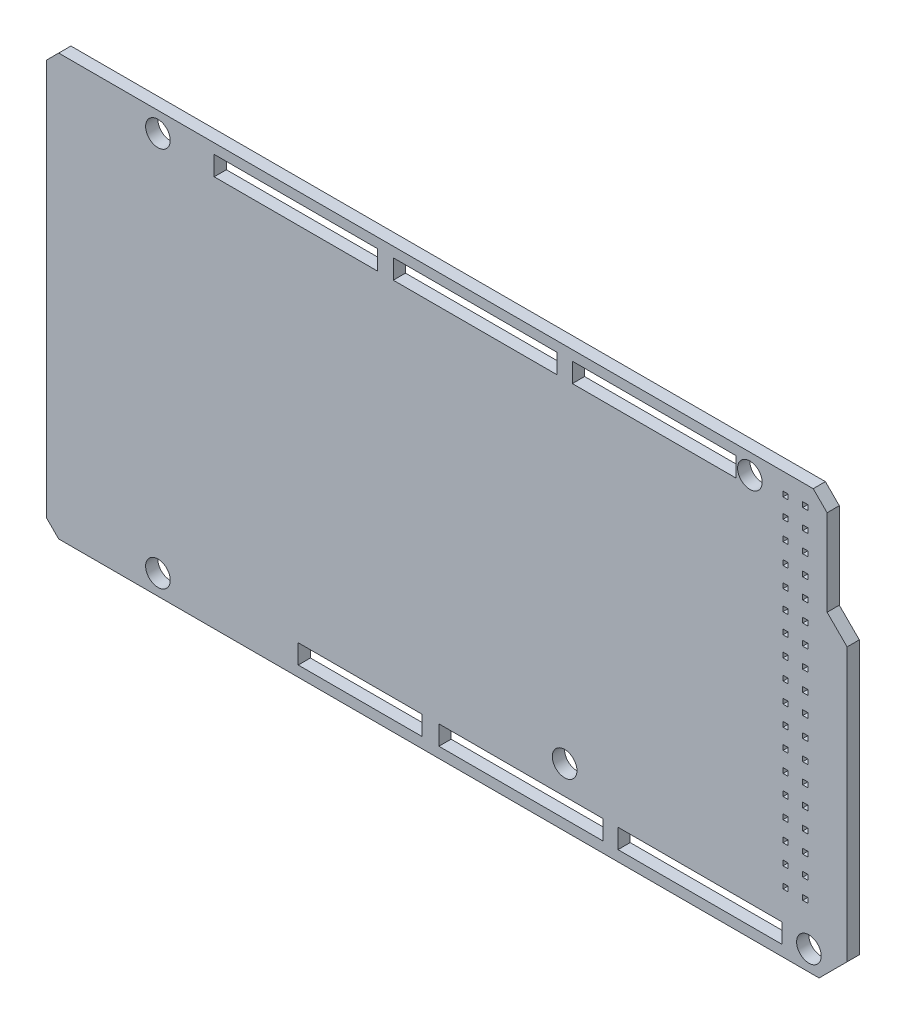
SolidWorks part; units mm, degrees
note: The reader was unsure of these and kept them because the rebuilt part matched: shared geometry of "Croquis3<3>".
ref_plane "Alzado" through (0, 0, 0) normal (0, 0, 1) x (1, 0, 0)
ref_plane "Planta" through (0, 0, 0) normal (0, 1, 0) x (1, 0, 0)
ref_plane "Vista lateral" through (0, 0, 0) normal (1, 0, 0) x (0, 0, -1)
sketch "Croquis1" plane through (0, 0, 0) normal (0, 0, 1) x (1, 0, 0)
  line L14 (46.5466, 27.6032) -> (48.31, 25.8397)
  line L15 (48.31, 25.8397) -> (48.31, 14.9032)
  line L16 (48.31, 14.9032) -> (50.85, 12.3632)
  line L17 (50.85, 12.3632) -> (50.85, -22.257)
  line L18 (47.294, -25.813) -> (50.85, -22.257)
  line L19 (47.294, -25.813) -> (-49.226, -25.813)
  line L20 (-50.75, -24.289) -> (-49.226, -25.813)
  line L21 (-50.75, -24.289) -> (-50.75, -22.003)
  line L22 (-50.75, -22.003) -> (-50.75, -12.859)
  line L23 (-50.75, 6.3942) -> (-50.75, 18.3322)
  line L24 (-50.75, -12.859) -> (-50.75, 6.3942)
  line L25 (-49.226, 27.6032) -> (46.5466, 27.6032)
  line L26 (-49.226, 27.6032) -> (-50.75, 26.0792)
  line L27 (-50.75, 18.3322) -> (-50.75, 26.0792)
  line L28 (-29.4902, 26.3332) -> (-29.4902, 23.8694)
  line L29 (-8.7384, 26.3332) -> (-29.4902, 26.3332)
  line L30 (-29.4902, 23.8694) -> (-8.7384, 23.8694)
  line L31 (-8.7384, 23.8694) -> (-8.7384, 26.3332)
  line L32 (-6.7572, 26.3332) -> (-6.7572, 23.8694)
  line L33 (13.9946, 26.3332) -> (-6.7572, 26.3332)
  line L34 (-6.7572, 23.8694) -> (13.9946, 23.8694)
  line L35 (15.9758, 26.3332) -> (15.9758, 23.8694)
  line L36 (36.7276, 26.3332) -> (15.9758, 26.3332)
  line L37 (15.9758, 23.8694) -> (36.7276, 23.8694)
  line L38 (36.7276, 23.8694) -> (36.7276, 26.3332)
  line L39 (46.786, 26.384) -> (41.8076, 26.384)
  line L40 (41.8076, 26.384) -> (41.8076, -19.8948)
  line L41 (46.786, -19.8948) -> (46.786, 26.384)
  line L42 (41.8076, -19.8948) -> (46.786, -19.8948)
  line L43 (42.595, -24.4668) -> (42.595, -22.003)
  line L44 (21.767, -24.4668) -> (42.595, -24.4668)
  line L45 (21.767, -22.003) -> (21.767, -24.4668)
  line L46 (19.862, -24.4668) -> (19.862, -22.003)
  line L47 (42.595, -22.003) -> (21.767, -22.003)
  line L48 (19.862, -22.003) -> (-0.966, -22.003)
  line L49 (-0.966, -24.4668) -> (19.862, -24.4668)
  line L50 (-0.966, -22.003) -> (-0.966, -24.4668)
  line L51 (-3.125, -24.4668) -> (-3.125, -22.0174)
  line L52 (-3.125, -22.0174) -> (-18.8222, -22.0174)
  line L53 (-18.8222, -24.4668) -> (-3.125, -24.4668)
  line L54 (-18.8222, -22.0174) -> (-18.8222, -24.4668)
  line L55 (13.9946, 26.3332) -> (13.9946, 23.8694)
  circle A5 centre (-36.6276, -23.273) radius 1.5621
  circle A6 centre (14.9979, -18.3945) radius 1.5621
  circle A7 centre (45.9986, -23.273) radius 1.5621
  circle A8 centre (-36.6276, 25.0632) radius 1.5621
  circle A9 centre (38.5056, 25.0632) radius 1.5621
  point P26 (-49.988, 26.8412)
  point P53 (0, 0)
  point P54 (0, 0)
extrude "Saliente-Extruir1" add sketch "Croquis1" along normal blind 1.55
sketch "Croquis2" plane through (0, 0, 0) normal (0, 0, -1) x (-1, 0, 0)
  line L1 (-46.786, 26.384) -> (-41.786, 26.384)
  line L2 (-46.786, 26.384) -> (-46.786, -19.8948)
  line L3 (-46.786, -19.8948) -> (-41.786, -19.8948)
  line L4 (-41.786, 26.384) -> (-41.786, -19.8948)
  dimension "D1" = 5
extrude "Cortar-Extruir1" cut sketch "Croquis2" against normal blind 95.55
sketch "Croquis3" plane through (0, 0, 0) normal (0, 0, -1) x (-1, 0, 0)
  line L0 (-46.786, 26.384) -> (-46.786, 25.104) construction
  line L1 (-46.786, -19.8948) -> (-46.786, 26.384) construction
  line L2 (-46.786, 25.104) -> (-41.786, 25.104) construction
  line L3 (-43.36, 20.5067) -> (-42.72, 20.5067)
  line L4 (-45.8587, 24.8652) -> (-45.2187, 24.8652)
  line L5 (-45.8587, 24.8652) -> (-45.8587, 25.5052)
  line L6 (-45.8587, 25.5052) -> (-45.2187, 25.5052)
  line L7 (-45.2187, 24.8652) -> (-45.2187, 25.5052)
  line L8 (-45.8587, 24.8652) -> (-45.2187, 25.5052) construction
  line L9 (-45.8587, 25.5052) -> (-45.2187, 24.8652) construction
  line L10 (-42.72, 20.5067) -> (-42.72, 19.866)
  line L11 (-43.36, 24.7836) -> (-42.72, 24.7836)
  line L12 (-43.36, 24.7836) -> (-43.36, 25.4243)
  line L13 (-43.36, 25.4243) -> (-42.72, 25.4243)
  line L14 (-42.72, 24.7836) -> (-42.72, 25.4243)
  line L15 (-43.36, 24.7836) -> (-42.72, 25.4243) construction
  line L16 (-43.36, 25.4243) -> (-42.72, 24.7836) construction
  line L17 (-41.786, -19.8948) -> (-41.786, 26.384) construction
  line L18 (-44.286, 25.104) -> (-44.286, 26.384) construction
  line L19 (-46.786, 22.6452) -> (-41.786, 22.6452) construction
  line L20 (-45.5387, 25.1852) -> (-45.5387, -19.8948) construction
  line L21 (-44.286, 25.104) -> (-44.286, -19.8948) construction
  line L22 (-41.786, -19.8948) -> (-46.786, -19.8948) construction
  line L23 (-43.04, 25.104) -> (-43.04, -19.8948) construction
  line L24 (-46.786, 20.1052) -> (-41.786, 20.1052) construction
  line L25 (-46.786, 17.5652) -> (-41.786, 17.5652) construction
  line L26 (-46.786, 15.0252) -> (-41.786, 15.0252) construction
  line L27 (-46.786, 12.4852) -> (-41.786, 12.4852) construction
  line L28 (-46.786, 9.9452) -> (-41.786, 9.9452) construction
  line L29 (-46.786, 7.4052) -> (-41.786, 7.4052) construction
  line L30 (-46.786, 4.8652) -> (-41.786, 4.8652) construction
  line L31 (-46.786, 2.3252) -> (-41.786, 2.3252) construction
  line L32 (-46.786, -0.2148) -> (-41.786, -0.2148) construction
  line L33 (-46.786, -2.7548) -> (-41.786, -2.7548) construction
  line L34 (-43.36, 19.866) -> (-42.72, 19.866)
  line L35 (-46.786, -5.2948) -> (-41.786, -5.2948) construction
  line L36 (-46.786, -7.8348) -> (-41.786, -7.8348)
  line L37 (-46.786, -10.3748) -> (-41.786, -10.3748) construction
  line L38 (-46.786, -12.9148) -> (-41.786, -12.9148) construction
  line L39 (-46.786, -15.4548) -> (-41.786, -15.4548) construction
  line L40 (-46.786, -17.9948) -> (-41.786, -17.9948) construction
  line L41 (-43.36, 20.5067) -> (-43.36, 19.866)
  line L42 (-45.2187, 20.4252) -> (-45.2187, 19.7852)
  line L43 (-45.8587, 20.4252) -> (-45.2187, 20.4252)
  line L44 (-45.8587, 22.9652) -> (-45.2187, 22.9652)
  line L45 (-45.8587, 22.9652) -> (-45.8587, 22.3252)
  line L46 (-45.8587, 22.3252) -> (-45.2187, 22.3252)
  line L47 (-45.2187, 22.9652) -> (-45.2187, 22.3252)
  line L48 (-45.8587, 22.9652) -> (-45.2187, 22.3252) construction
  line L49 (-45.8587, 22.3252) -> (-45.2187, 22.9652) construction
  line L50 (-45.8587, 20.4252) -> (-45.8587, 19.7852)
  line L51 (-45.8587, 19.7852) -> (-45.2187, 19.7852)
  line L52 (-45.5387, 22.6452) -> (-43.036, 22.6452) construction
  line L53 (-45.8587, 19.7852) -> (-45.8587, 15.0252) construction
  line L54 (-43.356, 22.3252) -> (-42.716, 22.3252)
  line L55 (-43.356, 22.3252) -> (-43.356, 22.9652)
  line L56 (-43.356, 22.9652) -> (-42.716, 22.9652)
  line L57 (-42.716, 22.3252) -> (-42.716, 22.9652)
  line L58 (-43.356, 22.3252) -> (-42.716, 22.9652) construction
  line L59 (-43.356, 22.9652) -> (-42.716, 22.3252) construction
  line L60 (-45.2187, 19.7852) -> (-45.2187, 15.0252) construction
  line L61 (-45.8587, 15.0252) -> (-45.8587, -0.2148) construction
  line L62 (-45.2187, 15.0252) -> (-45.2187, -0.2148) construction
  line L63 (-45.8587, -0.2148) -> (-45.8587, -19.8948) construction
  line L64 (-45.2187, -0.2148) -> (-45.2187, -19.8948) construction
  line L65 (-43.36, 19.866) -> (-43.36, 17.5652) construction
  line L70 (-42.72, 19.866) -> (-42.72, 17.5652) construction
  line L71 (-43.36, 17.5652) -> (-43.36, 15.0252) construction
  line L72 (-42.72, 17.5652) -> (-42.72, 15.0252) construction
  line L73 (-43.36, 15.0252) -> (-43.36, 7.4052) construction
  line L74 (-42.72, 15.0252) -> (-42.72, 4.8652) construction
  line L75 (-42.72, 4.8652) -> (-42.72, -19.8948) construction
  line L76 (-43.36, 7.4052) -> (-43.36, -19.8948) construction
  line L77 (-45.5387, -17.9948) -> (-43.04, -17.9948) construction
  line L78 (-45.8587, -18.3148) -> (-45.2187, -18.3148)
  line L79 (-45.8587, -18.3148) -> (-45.8587, -17.6748)
  line L80 (-45.8587, -17.6748) -> (-45.2187, -17.6748)
  line L81 (-45.2187, -18.3148) -> (-45.2187, -17.6748)
  line L82 (-45.8587, -18.3148) -> (-45.2187, -17.6748) construction
  line L83 (-45.8587, -17.6748) -> (-45.2187, -18.3148) construction
  line L84 (-43.36, -12.5948) -> (-42.72, -12.5948)
  line L85 (-43.36, -18.3148) -> (-42.72, -18.3148)
  line L86 (-43.36, -18.3148) -> (-43.36, -17.6748)
  line L87 (-43.36, -17.6748) -> (-42.72, -17.6748)
  line L88 (-42.72, -18.3148) -> (-42.72, -17.6748)
  line L89 (-43.36, -18.3148) -> (-42.72, -17.6748) construction
  line L90 (-43.36, -17.6748) -> (-42.72, -18.3148) construction
  line L91 (-42.72, -12.5948) -> (-42.72, -13.2348)
  line L92 (-43.36, -13.2348) -> (-42.72, -13.2348)
  line L93 (-43.36, -12.5948) -> (-43.36, -13.2348)
  line L94 (-45.2187, -12.5948) -> (-45.2187, -13.2348)
  line L95 (-45.8587, -12.5948) -> (-45.2187, -12.5948)
  line L96 (-45.8587, -12.5948) -> (-45.8587, -13.2348)
  line L97 (-45.8587, -13.2348) -> (-45.2187, -13.2348)
  line L98 (-46.786, -15.4548) -> (-45.5387, -15.4548) construction
  line L99 (-45.5387, -15.4548) -> (-43.04, -15.4548) construction
  line L100 (-46.786, -10.3748) -> (-45.5387, -10.3748) construction
  line L101 (-45.8587, -15.7748) -> (-45.2187, -15.7748)
  line L102 (-45.8587, -15.7748) -> (-45.8587, -15.1348)
  line L103 (-45.8587, -15.1348) -> (-45.2187, -15.1348)
  line L104 (-45.2187, -15.7748) -> (-45.2187, -15.1348)
  line L105 (-45.8587, -15.7748) -> (-45.2187, -15.1348) construction
  line L106 (-45.8587, -15.1348) -> (-45.2187, -15.7748) construction
  line L107 (-43.36, -15.7748) -> (-42.72, -15.7748)
  line L108 (-43.36, -15.7748) -> (-43.36, -15.1348)
  line L109 (-43.36, -15.1348) -> (-42.72, -15.1348)
  line L110 (-42.72, -15.7748) -> (-42.72, -15.1348)
  line L111 (-43.36, -15.7748) -> (-42.72, -15.1348) construction
  line L112 (-43.36, -15.1348) -> (-42.72, -15.7748) construction
  line L113 (-45.5387, -10.3748) -> (-43.04, -10.3748) construction
  line L114 (-43.36, -4.9748) -> (-42.72, -4.9748)
  line L115 (-45.8587, -10.6948) -> (-45.2187, -10.6948)
  line L116 (-45.8587, -10.6948) -> (-45.8587, -10.0548)
  line L117 (-45.8587, -10.0548) -> (-45.2187, -10.0548)
  line L118 (-45.2187, -10.6948) -> (-45.2187, -10.0548)
  line L119 (-45.8587, -10.6948) -> (-45.2187, -10.0548) construction
  line L120 (-45.8587, -10.0548) -> (-45.2187, -10.6948) construction
  line L121 (-43.36, -10.6948) -> (-42.72, -10.6948)
  line L122 (-43.36, -10.6948) -> (-43.36, -10.0548)
  line L123 (-43.36, -10.0548) -> (-42.72, -10.0548)
  line L124 (-42.72, -10.6948) -> (-42.72, -10.0548)
  line L125 (-43.36, -10.6948) -> (-42.72, -10.0548) construction
  line L126 (-43.36, -10.0548) -> (-42.72, -10.6948) construction
  line L127 (-42.72, -4.9748) -> (-42.72, -5.6148)
  line L128 (-43.36, -5.6148) -> (-42.72, -5.6148)
  line L129 (-43.36, -4.9748) -> (-43.36, -5.6148)
  line L130 (-45.2187, -4.9748) -> (-45.2187, -5.6148)
  line L131 (-45.8587, -4.9748) -> (-45.2187, -4.9748)
  line L132 (-45.8587, -4.9748) -> (-45.8587, -5.6148)
  line L133 (-45.8587, -5.6148) -> (-45.2187, -5.6148)
  line L134 (-46.786, -7.8348) -> (-45.5387, -7.8348) construction
  line L135 (-45.5387, -7.8348) -> (-43.04, -7.8348) construction
  line L136 (-45.2187, -7.5148) -> (-42.72, -7.5148) construction
  line L137 (-45.8586, -8.1548) -> (-45.2187, -8.1548)
  line L138 (-45.8586, -8.1548) -> (-45.8586, -7.5148)
  line L139 (-45.8586, -7.5148) -> (-45.2187, -7.5148)
  line L140 (-45.2187, -8.1548) -> (-45.2187, -7.5148)
  line L141 (-45.8586, -8.1548) -> (-45.2187, -7.5148) construction
  line L142 (-45.8586, -7.5148) -> (-45.2187, -8.1548) construction
  line L143 (-45.2187, -8.1548) -> (-42.72, -8.1548) construction
  line L144 (-46.786, -2.7548) -> (-45.5387, -2.7548) construction
  line L145 (-43.36, -8.1548) -> (-42.72, -8.1548)
  line L146 (-43.36, -8.1548) -> (-43.36, -7.5148)
  line L147 (-43.36, -7.5148) -> (-42.72, -7.5148)
  line L148 (-42.72, -8.1548) -> (-42.72, -7.5148)
  line L149 (-43.36, -8.1548) -> (-42.72, -7.5148) construction
  line L150 (-43.36, -7.5148) -> (-42.72, -8.1548) construction
  line L151 (-45.2187, -2.4348) -> (-42.72, -2.4348) construction
  line L152 (-45.8587, -3.0748) -> (-45.2187, -3.0748)
  line L153 (-45.8587, -3.0748) -> (-45.8587, -2.4348)
  line L154 (-45.8587, -2.4348) -> (-45.2187, -2.4348)
  line L155 (-45.2187, -3.0748) -> (-45.2187, -2.4348)
  line L156 (-45.8587, -3.0748) -> (-45.2187, -2.4348) construction
  line L157 (-45.8587, -2.4348) -> (-45.2187, -3.0748) construction
  line L158 (-45.2187, -3.0748) -> (-42.72, -3.0748) construction
  line L159 (-43.36, 2.6452) -> (-42.72, 2.6452)
  line L160 (-43.36, -3.0748) -> (-42.72, -3.0748)
  line L161 (-43.36, -3.0748) -> (-43.36, -2.4348)
  line L162 (-43.36, -2.4348) -> (-42.72, -2.4348)
  line L163 (-42.72, -3.0748) -> (-42.72, -2.4348)
  line L164 (-43.36, -3.0748) -> (-42.72, -2.4348) construction
  line L165 (-43.36, -2.4348) -> (-42.72, -3.0748) construction
  line L166 (-42.72, 2.6452) -> (-42.72, 2.0052)
  line L167 (-43.36, 2.0052) -> (-42.72, 2.0052)
  line L168 (-43.36, 2.6452) -> (-43.36, 2.0052)
  line L169 (-45.8587, 2.6452) -> (-45.2187, 2.6452)
  line L170 (-45.2187, 2.6452) -> (-45.2187, 2.0052)
  line L171 (-45.8587, 2.0052) -> (-45.2187, 2.0052)
  line L172 (-45.8587, 2.6452) -> (-45.8587, 2.0052)
  line L173 (-46.786, -0.2148) -> (-45.5387, -0.2148) construction
  line L174 (-45.5387, -0.2148) -> (-43.04, -0.2148) construction
  line L175 (-43.36, 7.7252) -> (-42.72, 7.7252)
  line L176 (-45.8587, -0.5348) -> (-45.2187, -0.5348)
  line L177 (-45.8587, -0.5348) -> (-45.8587, 0.1052)
  line L178 (-45.8587, 0.1052) -> (-45.2187, 0.1052)
  line L179 (-45.2187, -0.5348) -> (-45.2187, 0.1052)
  line L180 (-45.8587, -0.5348) -> (-45.2187, 0.1052) construction
  line L181 (-45.8587, 0.1052) -> (-45.2187, -0.5348) construction
  line L182 (-43.36, -0.5348) -> (-42.72, -0.5348)
  line L183 (-43.36, -0.5348) -> (-43.36, 0.1052)
  line L184 (-43.36, 0.1052) -> (-42.72, 0.1052)
  line L185 (-42.72, -0.5348) -> (-42.72, 0.1052)
  line L186 (-43.36, -0.5348) -> (-42.72, 0.1052) construction
  line L187 (-43.36, 0.1052) -> (-42.72, -0.5348) construction
  line L188 (-42.72, 7.0852) -> (-42.72, 7.7252)
  line L189 (-43.36, 7.0852) -> (-42.72, 7.0852)
  line L190 (-43.36, 7.0852) -> (-43.36, 7.7252)
  line L191 (-45.8587, 7.7252) -> (-45.2187, 7.7252)
  line L192 (-45.2187, 7.0852) -> (-45.2187, 7.7252)
  line L193 (-45.8587, 7.0852) -> (-45.8587, 7.7252)
  line L194 (-45.8587, 7.0852) -> (-45.2187, 7.0852)
  line L195 (-46.786, 4.8652) -> (-45.5387, 4.8652) construction
  line L196 (-45.5387, 4.8652) -> (-43.04, 4.8652) construction
  line L197 (-45.2187, 5.1852) -> (-42.72, 5.1852) construction
  line L198 (-45.8587, 4.5452) -> (-45.2187, 4.5452)
  line L199 (-45.8587, 4.5452) -> (-45.8587, 5.1852)
  line L200 (-45.8587, 5.1852) -> (-45.2187, 5.1852)
  line L201 (-45.2187, 4.5452) -> (-45.2187, 5.1852)
  line L202 (-45.8587, 4.5452) -> (-45.2187, 5.1852) construction
  line L203 (-45.8587, 5.1852) -> (-45.2187, 4.5452) construction
  line L204 (-45.2187, 4.5452) -> (-42.72, 4.5452) construction
  line L205 (-43.36, 5.1852) -> (-42.72, 5.1852)
  line L206 (-42.72, 5.1852) -> (-42.72, 4.5452)
  line L207 (-42.72, 4.5452) -> (-43.36, 4.5452)
  line L208 (-43.36, 4.5452) -> (-43.36, 5.1852)
  line L209 (-43.36, 12.8052) -> (-42.72, 12.8052)
  line L210 (-42.72, 12.8052) -> (-42.72, 12.1652)
  line L211 (-43.36, 12.1652) -> (-42.72, 12.1652)
  line L212 (-43.36, 12.8052) -> (-43.36, 12.1652)
  line L213 (-45.2187, 12.8052) -> (-45.2187, 12.1652)
  line L214 (-45.8587, 12.8052) -> (-45.2187, 12.8052)
  line L215 (-45.8587, 12.8052) -> (-45.8587, 12.1652)
  line L216 (-45.8587, 12.1652) -> (-45.2187, 12.1652)
  line L217 (-46.786, 9.9452) -> (-45.5387, 9.9452) construction
  line L218 (-45.5387, 9.9452) -> (-43.04, 9.9452) construction
  line L219 (-43.36, 17.8852) -> (-42.72, 17.8852)
  line L220 (-45.8587, 9.6252) -> (-45.2187, 9.6252)
  line L221 (-45.8587, 9.6252) -> (-45.8587, 10.2652)
  line L222 (-45.8587, 10.2652) -> (-45.2187, 10.2652)
  line L223 (-45.2187, 9.6252) -> (-45.2187, 10.2652)
  line L224 (-45.8587, 9.6252) -> (-45.2187, 10.2652) construction
  line L225 (-45.8587, 10.2652) -> (-45.2187, 9.6252) construction
  line L226 (-43.36, 9.6252) -> (-42.72, 9.6252)
  line L227 (-43.36, 9.6252) -> (-43.36, 10.2652)
  line L228 (-43.36, 10.2652) -> (-42.72, 10.2652)
  line L229 (-42.72, 9.6252) -> (-42.72, 10.2652)
  line L230 (-43.36, 9.6252) -> (-42.72, 10.2652) construction
  line L231 (-43.36, 10.2652) -> (-42.72, 9.6252) construction
  line L232 (-42.72, 17.2452) -> (-42.72, 17.8852)
  line L233 (-43.36, 17.2452) -> (-42.72, 17.2452)
  line L234 (-43.36, 17.2452) -> (-43.36, 17.8852)
  line L235 (-45.2187, 17.2452) -> (-45.2187, 17.8852)
  line L236 (-45.8587, 17.8852) -> (-45.2187, 17.8852)
  line L237 (-45.8587, 17.2452) -> (-45.8587, 17.8852)
  line L238 (-45.8587, 17.2452) -> (-45.2187, 17.2452)
  line L239 (-46.786, 15.0252) -> (-45.5387, 15.0252) construction
  line L240 (-45.5387, 15.0252) -> (-43.04, 15.0252) construction
  line L242 (-45.8587, 14.7052) -> (-45.2187, 14.7052)
  line L243 (-45.8587, 14.7052) -> (-45.8587, 15.3452)
  line L244 (-45.8587, 15.3452) -> (-45.2187, 15.3452)
  line L245 (-45.2187, 14.7052) -> (-45.2187, 15.3452)
  line L246 (-45.8587, 14.7052) -> (-45.2187, 15.3452) construction
  line L247 (-45.8587, 15.3452) -> (-45.2187, 14.7052) construction
  line L248 (-43.36, 14.7052) -> (-42.72, 14.7052)
  line L249 (-43.36, 14.7052) -> (-43.36, 15.3452)
  line L250 (-43.36, 15.3452) -> (-42.72, 15.3452)
  line L251 (-42.72, 14.7052) -> (-42.72, 15.3452)
  line L252 (-43.36, 14.7052) -> (-42.72, 15.3452) construction
  line L253 (-43.36, 15.3452) -> (-42.72, 14.7052) construction
  point P61 (-45.5387, 22.6452)
  point P83 (-45.5387, -17.9948)
  point P155 (-43.04, -2.7548)
  dimension "D1" = 1.28
  dimension "D2" = 1.25
  dimension "D3" = 0.64
  dimension "D4" = 0.64
  dimension "D5" = 2.5
  dimension "D6" = 0.64
  dimension "D7" = 2.54
  dimension "D8" = 2.54
  dimension "D9" = 2.54
  dimension "D18" = 2.54
  dimension "D24" = 0.64
  dimension "D25" = 0.64
  dimension "D26" = 0.64
  dimension "D27" = 0.64
  dimension "D28" = 0.64
  dimension "D29" = 0.64
  dimension "D30" = 0.64
  dimension "D31" = 0.64
  dimension "D32" = 0.64
  dimension "D33" = 0.64
  dimension "D34" = 0.64
  dimension "D35" = 0.64
  dimension "D36" = 0.64
  dimension "D37" = 0.64
  dimension "D38" = 0.64
  dimension "D39" = 0.64
  dimension "D40" = 0.64
  dimension "D10" = 2.54
  dimension "D11" = 2.54
  dimension "D12" = 2.54
  dimension "D13" = 2.54
  dimension "D14" = 2.54
  dimension "D15" = 2.54
  dimension "D16" = 2.54
  dimension "D17" = 2.54
  dimension "D19" = 2.54
  dimension "D20" = 2.54
  dimension "D21" = 2.54
  dimension "D22" = 2.54
  dimension "D23" = 2.54
extrude "Saliente-Extruir2" add sketch "Croquis3" against normal up to surface (1.55 mm away) contours L148 L145 L146 L36 L140 L137 L138 L79 L80 L88 L124 L121 L122 L123 L118 L115 L116 L117 L110 L107 L108 L109 L104 L101 L102 L103 L97 L96 L95 L94 L93 L84 L91 L92 L85 L86 L87 L81 L78
extrude "Saliente-Extruir3" add sketch "Croquis3<3>" against normal up to surface (1.55 mm away) contours L148 L36 L88 L87 L79 L138 L139 L140 L146 L147 L251 L248 L249 L250 L245 L242 L243 L244 L238 L237 L236 L235 L229 L226 L227 L228 L223 L220 L221 L222 L216 L215 L214 L213 L212 L209 L210 L211 L201 L198 L199
sketch "Croquis3<3>" plane through (0, 0, 0) normal (0, 0, -1) x (-1, 0, 0) same geometry as "Croquis3"
sketch "Croquis4" plane through (50.85, 0, 0) normal (1, 0, 0) x (0, 0, -1)
  line L1 (-1.55, -25.813) -> (0.01, -25.813)
  line L2 (-1.55, -25.813) -> (-1.55, 27.6032)
  line L3 (-1.55, 27.6032) -> (0.01, 27.6032)
  line L4 (0.01, -25.813) -> (0.01, 27.6032)
  dimension "D1" = 1.56
